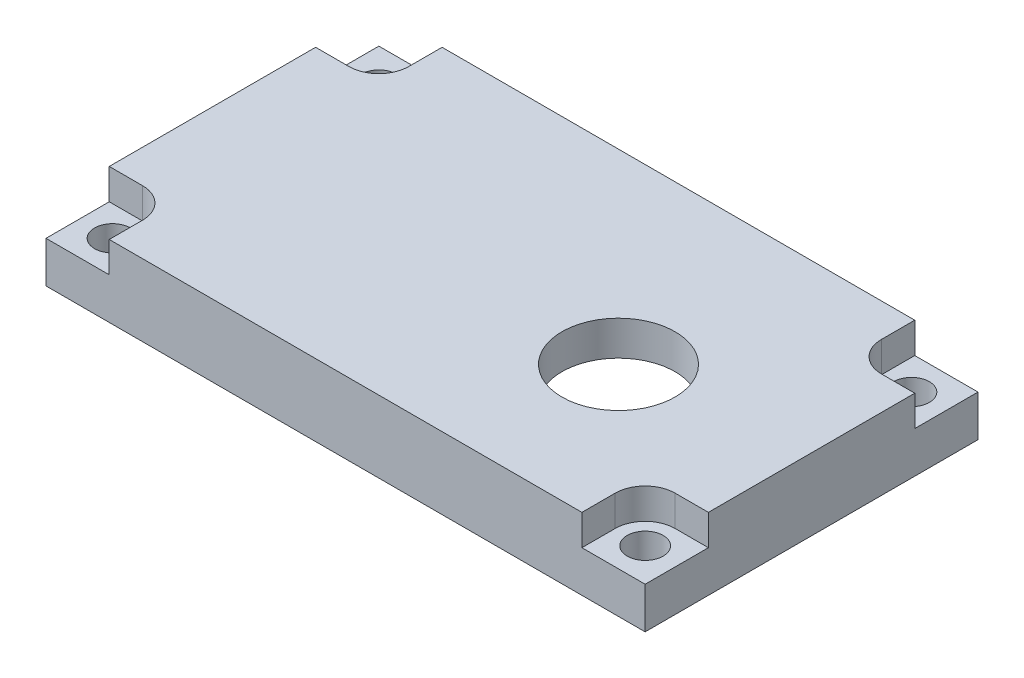
SolidWorks part; units mm, degrees
ref_plane "前基準面" through (0, 0, 0) normal (0, 0, 1) x (1, 0, 0)
ref_plane "上基準面" through (0, 0, 0) normal (0, 1, 0) x (1, 0, 0)
ref_plane "右基準面" through (0, 0, 0) normal (1, 0, 0) x (0, 0, -1)
sketch "草圖1" plane through (0, 0, 0) normal (0, 1, 0) x (1, 0, 0)
  line L1 (22.5, -12.5) -> (-22.5, -12.5)
  line L2 (22.5, -12.5) -> (22.5, 12.5)
  line L3 (22.5, 12.5) -> (-22.5, 12.5)
  line L4 (-22.5, -12.5) -> (-22.5, 12.5)
  line L5 (22.5, -12.5) -> (-22.5, 12.5) construction
  line L6 (22.5, 12.5) -> (-22.5, -12.5) construction
  point P0 (0, 0)
  dimension "D1" = 25
  dimension "D2" = 45
extrude "填料-伸長1" add sketch "草圖1" along normal blind 5.4
sketch "草圖2" plane through (0, 5.4, 0) normal (0, 1, 0) x (1, 0, 0)
  line L0 (-22.5, 12.5) -> (-22.5, -12.5) construction
  line L1 (20, -10) -> (-20, -10) construction
  line L2 (20, -10) -> (20, 10) construction
  line L3 (20, 10) -> (-20, 10) construction
  line L4 (-20, -10) -> (-20, 10) construction
  line L5 (20, -10) -> (-20, 10) construction
  line L6 (20, 10) -> (-20, -10) construction
  line L7 (22.5, 12.5) -> (-22.5, 12.5) construction
  circle A0 centre (-20, 10) radius 1.35
  circle A1 centre (-20, -10) radius 1.35
  circle A2 centre (20, -10) radius 1.35
  circle A3 centre (20, 10) radius 1.35
  point P0 (0, 0)
  dimension "D3" = 2.7
  dimension "D1" = 2.5
  dimension "D2" = 2.5
extrude "除料-伸長1" cut sketch "草圖2" against normal through all
sketch "草圖3" plane through (0, 5.4, 0) normal (0, 1, 0) x (1, 0, 0)
  line L0 (-20, -7.75) -> (-22.5, -7.75)
  line L1 (-22.5, 12.5) -> (-22.5, -12.5) construction
  line L2 (-22.5, -7.75) -> (-22.5, -12.5)
  line L3 (-22.5, -12.5) -> (-17.75, -12.5)
  line L4 (-22.5, -12.5) -> (22.5, -12.5) construction
  line L5 (-17.75, -12.5) -> (-17.75, -10)
  arc A0 (-20, -7.75) -> (-17.75, -10) centre (-20, -10) cw
  dimension "D1" = 2.25
extrude "除料-伸長2" cut sketch "草圖3" against normal blind 2.3
mirror "鏡射1" about plane through (0, 0, 0) normal (0, 0, 1) of "除料-伸長2"
mirror "鏡射2" about plane through (0, 0, 0) normal (1, 0, 0) of "鏡射1"
shell "薄殼1" thickness 1.5 removed face at (20, 0, -8.65)
sketch "草圖4" plane through (0, 5.4, 0) normal (0, 1, 0) x (1, 0, 0)
  line L0 (22.5, -7.75) -> (22.5, 7.75) construction
  line L1 (-17.75, -12.5) -> (17.75, -12.5) construction
  circle A0 centre (9.5, -1.5) radius 4.25
  dimension "D3" = 8.5
  dimension "D1" = 13
  dimension "D2" = 11
extrude "除料-伸長3" cut sketch "草圖4" against normal through all
sketch "草圖5" plane through (0, 3.9, 0) normal (0, -1, 0) x (1, 0, 0)
  circle A0 centre (-0.5, 1.5) radius 2
  circle A1 centre (9.5, 1.5) radius 4.25 construction
  point P5 (9.5, 1.5)
  dimension "D2" = 4
  dimension "D1" = 10
extrude "填料-伸長2" [suppressed] add sketch "草圖5" along normal blind 0.6
sketch "草圖6" plane through (0, 3.9, 0) normal (0, -1, 0) x (1, 0, 0)
  circle A0 centre (9.5, 1.5) radius 4.25 construction
  circle A1 centre (9.5, 1.5) radius 4.25
  circle A2 centre (9.5, 1.5) radius 5.75
  dimension "D1" = 1.5
extrude "填料-伸長3" add sketch "草圖6" along normal blind 1.1
sketch "草圖7" plane through (0, 3.9, 0) normal (0, -1, 0) x (1, 0, 0)
  circle A0 centre (-9.5, 1.5) radius 2.25
  circle A1 centre (-9.5, 1.5) radius 1.25
  circle A2 centre (9.5, 1.5) radius 4.25 construction
  point P10 (9.5, 1.5)
  dimension "D2" = 4.5
  dimension "D3" = 2.5
  dimension "D1" = 19
extrude "填料-伸長4" add sketch "草圖7" along normal blind 0.6
